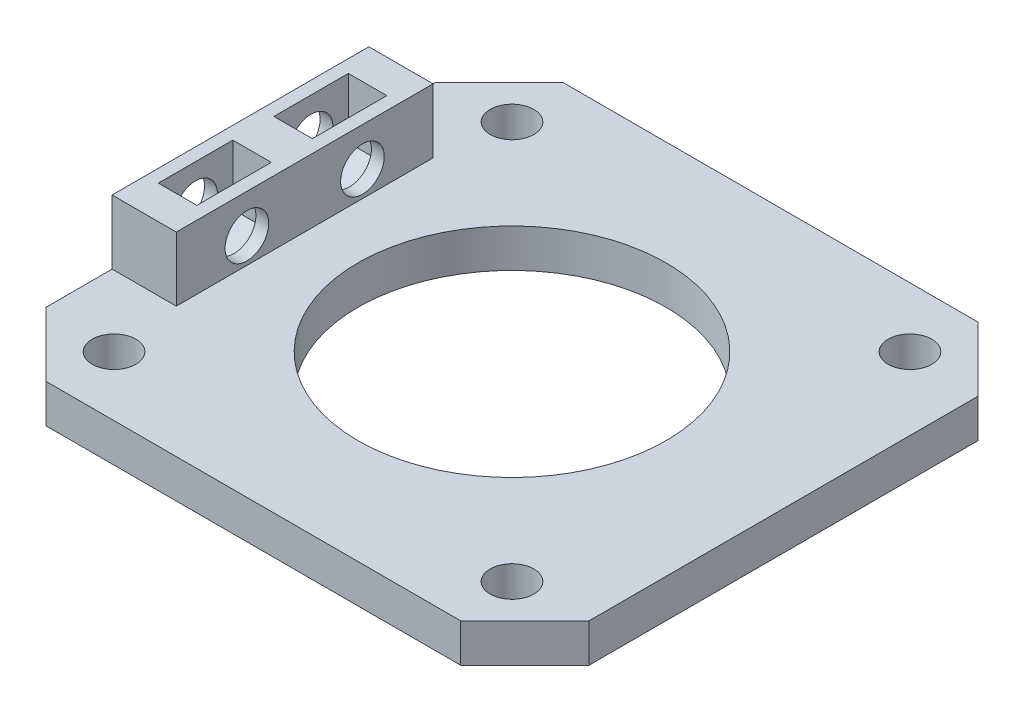
SolidWorks part; units mm, degrees
ref_plane "Alzado" through (0, 0, 0) normal (0, 0, 1) x (1, 0, 0)
ref_plane "Planta" through (0, 0, 0) normal (0, 1, 0) x (1, 0, 0)
ref_plane "Vista lateral" through (0, 0, 0) normal (1, 0, 0) x (0, 0, -1)
sketch "Croquis1" plane through (0, 0, 0) normal (0, 1, 0) x (1, 0, 0)
  line L1 (21.15, -20.15) -> (-21.15, -20.15)
  line L2 (21.15, -20.15) -> (21.15, 20.15)
  line L3 (21.15, 20.15) -> (-21.15, 20.15)
  line L4 (-21.15, -20.15) -> (-21.15, 20.15)
  line L7 (15.5, -15.5) -> (-15.5, -15.5) construction
  line L8 (15.5, -15.5) -> (15.5, 15.5) construction
  line L9 (15.5, 15.5) -> (-15.5, 15.5) construction
  line L10 (-15.5, -15.5) -> (-15.5, 15.5) construction
  line L11 (15.5, -15.5) -> (-15.5, 15.5) construction
  line L12 (15.5, 15.5) -> (-15.5, -15.5) construction
  circle A0 centre (0, 0) radius 12
  circle A1 centre (-15.5, 15.5) radius 1.7
  circle A2 centre (15.5, 15.5) radius 1.7
  circle A3 centre (-15.5, -15.5) radius 1.7
  circle A4 centre (15.5, -15.5) radius 1.7
  point P0 (0, 0)
  point P6 (0, 0)
  point P17 (-21.15, 0)
  point P18 (0, 20.15)
  point P19 (0, 0)
  point P20 (0, 0)
  dimension "D4" = 3.4
  dimension "D5" = 24
  dimension "D1" = 40.3
  dimension "D2" = 42.3
  dimension "D3" = 31
  dimension "D6" = 31
extrude "Saliente-Extruir1" add sketch "Croquis1" along normal blind 3
fillet "Chaflán2" radius 5 1 edges at (21.15, 1.5, -20.15) type face fillet profile chamfer first side face at (0, 1.5, -20.15) second side face at (21.15, 1.5, 0)
fillet "Chaflán3" radius 5 1 edges at (21.15, 1.5, 20.15) type face fillet profile chamfer first side face at (0, 1.5, 20.15) second side face at (21.15, 1.5, 2.5)
fillet "Chaflán4" radius 5 1 edges at (-21.15, 1.5, 20.15) type face fillet profile chamfer first side face at (-21.15, 1.5, 0) second side face at (-2.5, 1.5, 20.15)
fillet "Chaflán5" radius 5 1 edges at (-21.15, 1.5, -20.15) type face fillet profile chamfer first side face at (-21.15, 1.5, -2.5) second side face at (-2.5, 1.5, -20.15)
sketch "Croquis2" plane through (0, 3, 0) normal (0, 1, 0) x (1, 0, 0)
  line L0 (-21.15, 15.15) -> (-21.15, -15.15) construction
  line L1 (-16.15, -10) -> (-21.15, -10)
  line L2 (-16.15, -10) -> (-16.15, 10)
  line L3 (-16.15, 10) -> (-21.15, 10)
  line L4 (-21.15, -10) -> (-21.15, 10)
  line L5 (-16.15, -10) -> (-21.15, 10) construction
  line L6 (-16.15, 10) -> (-21.15, -10) construction
  point P0 (-18.65, 0)
  dimension "D1" = 5
  dimension "D2" = 20
extrude "Saliente-Extruir2" add sketch "Croquis2" along normal blind 5
sketch "Croquis3" plane through (-21.15, 0, 0) normal (-1, 0, 0) x (0, 0, 1)
  line L0 (-4.5, 5) -> (4.5, 5) construction
  circle A0 centre (-4.5, 5) radius 1.7
  circle A1 centre (4.5, 5) radius 1.7
  point P2 (0, 5)
  dimension "D1" = 3.4
  dimension "D2" = 9
  dimension "D3" = 5
extrude "Cortar-Extruir1" cut sketch "Croquis3" against normal blind 7
ref_plane "Plano1" through (-18.65, 0, 0) normal (1, 0, 0) x (0, 0, -1)
sketch "Croquis4" plane through (-18.65, 0, 0) normal (1, 0, 0) x (0, 0, -1)
  line L0 (-7.4012, 6.675) -> (-7.4012, 13.325)
  line L1 (-4.5, 8.35) -> (-7.4012, 6.675) construction
  line L2 (-7.4012, 6.675) -> (-7.4012, 3.325)
  line L3 (-7.4012, 3.325) -> (-4.5, 1.65)
  line L4 (-4.5, 1.65) -> (-1.5988, 3.325)
  line L5 (-1.5988, 3.325) -> (-1.5988, 6.675)
  line L6 (-1.5988, 6.675) -> (-4.5, 8.35) construction
  line L7 (4.5, 8.35) -> (1.5988, 6.675) construction
  line L8 (1.5988, 6.675) -> (1.5988, 3.325)
  line L9 (1.5988, 3.325) -> (4.5, 1.65)
  line L10 (4.5, 1.65) -> (7.4012, 3.325)
  line L11 (7.4012, 3.325) -> (7.4012, 6.675)
  line L12 (7.4012, 6.675) -> (4.5, 8.35) construction
  line L13 (-7.4012, 13.325) -> (-1.5988, 13.325)
  line L14 (-1.5988, 13.325) -> (-1.5988, 6.675)
  line L15 (1.5988, 6.675) -> (1.5988, 13.325)
  line L16 (1.5988, 13.325) -> (7.4012, 13.325)
  line L17 (7.4012, 13.325) -> (7.4012, 6.675)
  line L18 (-10, 8) -> (-10, 3) construction
  circle A0 centre (-4.5, 5) radius 3.35 construction
  circle A1 centre (4.5, 5) radius 3.35 construction
  dimension "D1" = 6.7
  dimension "D2" = 10
extrude "Cortar-Extruir2" cut sketch "Croquis4" against normal blind 1.5 and the other way blind 1.5
